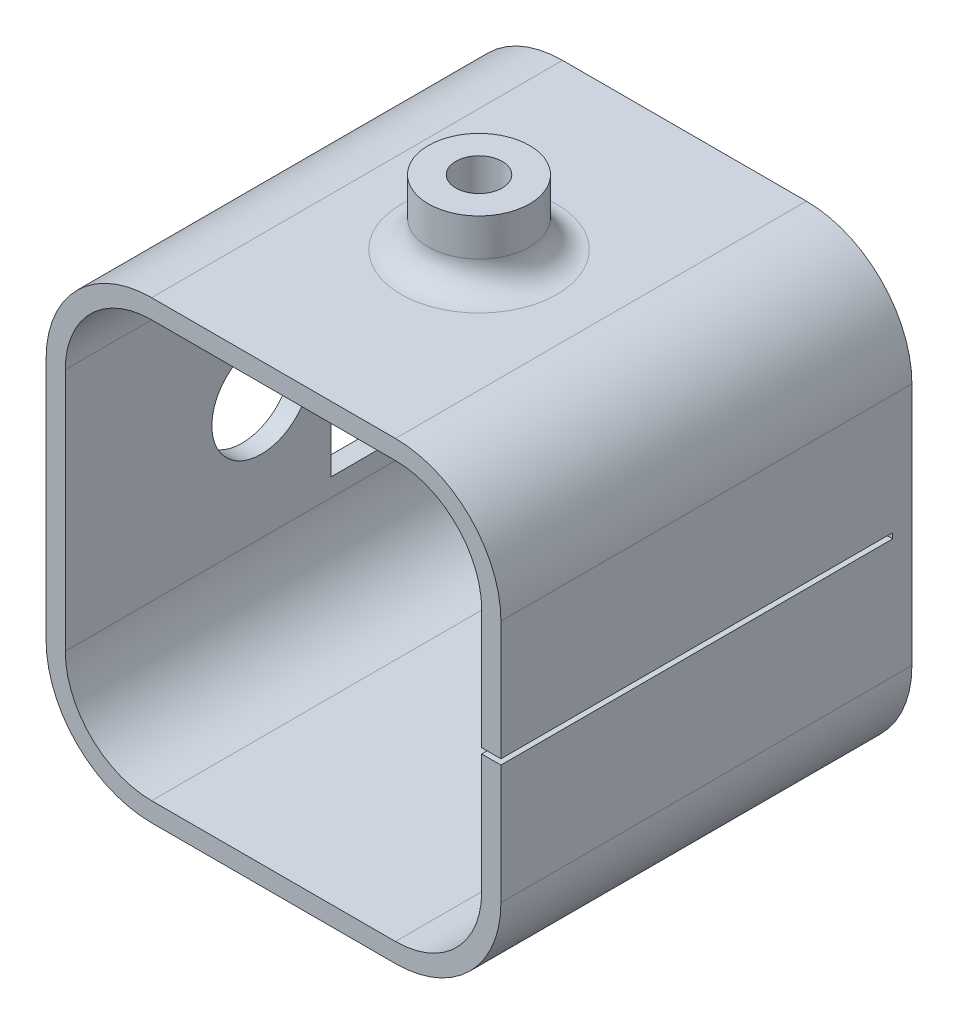
SolidWorks part; units mm, degrees
ref_plane "Front Plane" through (0, 0, 0) normal (0, 0, 1) x (1, 0, 0)
ref_plane "Top Plane" through (0, 0, 0) normal (0, 1, 0) x (1, 0, 0)
ref_plane "Right Plane" through (0, 0, 0) normal (1, 0, 0) x (0, 0, -1)
sketch "Sketch1" plane through (0, 0, 0) normal (0, 0, 1) x (1, 0, 0)
  line L0 (-11.304, 21.082) -> (11.304, 21.082)
  line L1 (-11.304, -19.304) -> (11.304, -19.304)
  line L2 (-19.304, -11.304) -> (-19.304, 11.304)
  line L3 (-11.304, 19.304) -> (11.304, 19.304)
  line L4 (19.304, -11.304) -> (19.304, 11.304)
  line L5 (-19.304, -19.304) -> (19.304, 19.304) construction
  line L6 (-19.304, 19.304) -> (19.304, -19.304) construction
  line L7 (21.082, -11.304) -> (21.082, 11.304)
  line L8 (-11.304, -21.082) -> (11.304, -21.082)
  line L9 (-21.082, -11.304) -> (-21.082, 11.304)
  arc A0 (-11.304, -19.304) -> (-19.304, -11.304) centre (-11.304, -11.304) cw
  arc A1 (11.304, -19.304) -> (19.304, -11.304) centre (11.304, -11.304) ccw
  arc A2 (11.304, 19.304) -> (19.304, 11.304) centre (11.304, 11.304) cw
  arc A3 (-19.304, 11.304) -> (-11.304, 19.304) centre (-11.304, 11.304) cw
  arc A4 (11.304, 21.082) -> (21.082, 11.304) centre (11.304, 11.304) cw
  arc A5 (11.304, -21.082) -> (21.082, -11.304) centre (11.304, -11.304) ccw
  arc A6 (-11.304, -21.082) -> (-21.082, -11.304) centre (-11.304, -11.304) cw
  arc A7 (-21.082, 11.304) -> (-11.304, 21.082) centre (-11.304, 11.304) cw
  point P0 (0, 0)
  dimension "D2" = 8
  dimension "D1" = 38.608
  dimension "D3" = 1.778
extrude "Boss-Extrude1" add sketch "Sketch1" along normal blind 36.322
sketch "Sketch2" plane through (-21.082, 0, 0) normal (-1, 0, 0) x (0, 0, 1)
  line L0 (36.322, -11.304) -> (0, -11.304) construction
  line L1 (0, 11.304) -> (0, -11.304) construction
  line L2 (11.684, 9.6266) -> (5.588, 9.6266)
  line L3 (11.684, 9.6266) -> (11.684, -9.6266)
  line L4 (11.684, -9.6266) -> (5.588, -9.6266)
  line L5 (5.588, 9.6266) -> (5.588, -9.6266)
  line L6 (11.684, 9.6266) -> (5.588, -9.6266) construction
  line L7 (11.684, -9.6266) -> (5.588, 9.6266) construction
  circle A0 centre (18.161, 0) radius 4.572
  point P2 (0, 0)
  point P5 (18.161, -11.304)
  point P6 (0, 0)
  point P8 (8.636, 0)
  point P13 (1.9776, -9.6266)
  dimension "D1" = 9.144
  dimension "D2" = 6.096
  dimension "D3" = 19.2532
  dimension "D4" = 5.588
extrude "Cut-Extrude1" cut sketch "Sketch2" against normal up to next
extrude "Boss-Extrude2" add sketch "Sketch1<2>" against normal blind 1.778 contours A3 L2 A0 L1 A1 L4 A2 L3 | A7 L9 A6 L8 A5 L7 A4 L0 L2 A3 L3 A2 L4 A1 L1 A0 region at (0, 20.4857, 0) region at (0, 0, 0)
sketch "Sketch1<2>" plane through (0, 0, 0) normal (0, 0, 1) x (1, 0, 0) same geometry as "Sketch1"
sketch "Sketch3" plane through (0, 0, -1.778) normal (0, 0, -1) x (-1, 0, 0)
  circle A0 centre (0, 0) radius 6.858
  dimension "D1" = 13.716
extrude "Cut-Extrude2" cut sketch "Sketch3" against normal up to next
sketch "Sketch4" plane through (0, 21.082, 0) normal (0, 1, 0) x (1, 0, 0)
  line L0 (-11.304, -36.322) -> (-11.304, 1.778) construction
  circle A0 centre (0, -17.272) radius 4.69
  circle A1 centre (0, -17.272) radius 2.15
  point P3 (0, 0)
  point P7 (-11.304, -17.272)
  dimension "D1" = 4.3
  dimension "D2" = 2.54
extrude "Boss-Extrude3" add sketch "Sketch4" along normal blind 6
mirror "Mirror1" about plane through (0, 0, 0) normal (0, 1, 0) of "Boss-Extrude3"
fillet "Fillet1" radius 2.54 2 edges at (0, -21.082, 21.962) (0, 21.082, 12.582)
sketch "Sketch5" plane through (0, 0, -1.778) normal (0, 0, -1) x (-1, 0, 0)
  line L0 (-19.304, -11.304) -> (-19.304, 11.304) construction
  line L1 (-19.304, 5.08) -> (-13.716, 5.08)
  line L2 (-19.304, 5.08) -> (-19.304, -5.08)
  line L3 (-19.304, -5.08) -> (-13.716, -5.08)
  line L4 (-13.716, 5.08) -> (-13.716, -5.08)
  line L5 (-19.304, 5.08) -> (-13.716, -5.08) construction
  line L6 (-19.304, -5.08) -> (-13.716, 5.08) construction
  line L7 (-19.304, -11.304) -> (-19.304, 11.304)
  point P0 (-16.51, 0)
  point P5 (0, 0)
  dimension "D1" = 5.588
  dimension "D2" = 10.16
extrude "Cut-Extrude3" cut sketch "Sketch5" against normal up to next contours L4 L1 L2 L3 region at (16.51, 0, -1.778)
fillet "Fillet2" radius 1.778 2 edges at (13.716, -5.08, -0.889) (13.716, 5.08, -0.889)
sketch "Sketch6" plane through (0, 0, 36.322) normal (0, 0, 1) x (1, 0, 0)
  line L0 (19.304, -11.304) -> (19.304, 11.304) construction
  line L1 (19.304, -0.25) -> (21.082, -0.25)
  line L2 (19.304, -0.25) -> (19.304, 0.25)
  line L3 (19.304, 0.25) -> (21.082, 0.25)
  line L4 (21.082, -0.25) -> (21.082, 0.25)
  line L5 (21.082, -11.304) -> (21.082, 11.304) construction
  point P8 (21.082, -1.0714)
  point P9 (21.082, 0)
  point P10 (19.304, 0)
  dimension "D1" = 0.5
extrude "Cut-Extrude4" cut sketch "Sketch6" against normal up to surface (36.322 mm away) up to face at (6.878, 0, 0)
